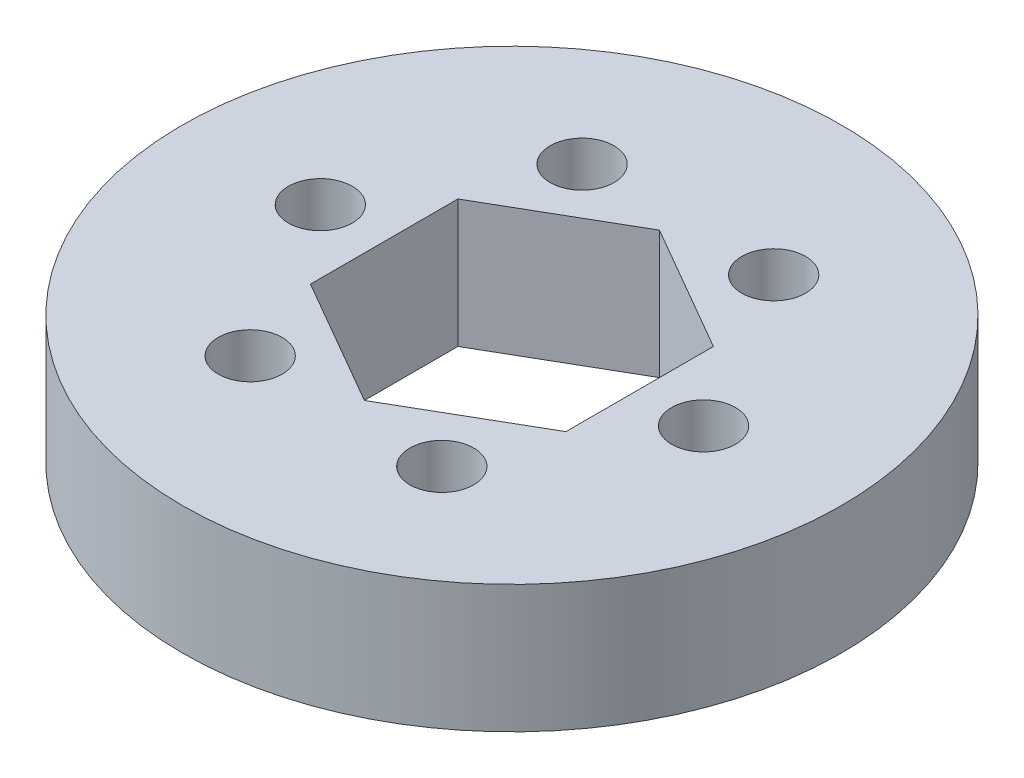
SolidWorks part; units mm, degrees
ref_plane "Front" through (0, 0, 0) normal (0, 0, 1) x (1, 0, 0)
ref_plane "Top" through (0, 0, 0) normal (0, 1, 0) x (1, 0, 0)
ref_plane "Right" through (0, 0, 0) normal (1, 0, 0) x (0, 0, -1)
sketch "Sketch1" plane through (0, 0, 0) normal (0, 1, 0) x (1, 0, 0)
  line L1 (0, 7.3323) -> (-6.35, 3.6662)
  line L2 (-6.35, 3.6662) -> (-6.35, -3.6662)
  line L3 (-6.35, -3.6662) -> (0, -7.3323)
  line L4 (0, -7.3323) -> (6.35, -3.6662)
  line L5 (6.35, -3.6662) -> (6.35, 3.6662)
  line L6 (6.35, 3.6662) -> (0, 7.3323)
  circle A0 centre (0, 0) radius 6.35 construction
  circle A1 centre (0, 0) radius 16.383
  dimension "D1" = 32.766
extrude "Boss-Extrude1" add sketch "Sketch1" along normal blind 6.35
sketch "Sketch2" plane through (0, 6.35, 0) normal (0, 1, 0) x (1, 0, 0)
  line L4 (0, 0) -> (6.35, 0) construction
  line L5 (6.35, -3.6662) -> (6.35, 3.6662) construction
  line L6 (0, 0) -> (0, 7.3323) construction
sketch "Sketch3" plane through (0, 6.35, 0) normal (0, 1, 0) x (1, 0, 0)
  line L0 (0, 0) -> (9.525, 0) construction
  circle A0 centre (9.525, 0) radius 1.5875
  circle A1 centre (4.7625, -8.2489) radius 1.5875
  circle A2 centre (-4.7625, -8.2489) radius 1.5875
  circle A3 centre (-9.525, 0) radius 1.5875
  circle A4 centre (-4.7625, 8.2489) radius 1.5875
  circle A5 centre (4.7625, 8.2489) radius 1.5875
  point P16 (0, 0)
  dimension "D1" = 3.175
  dimension "D2" = 9.525
  dimension "D3" = 6
extrude "Cut-Extrude1" cut sketch "Sketch3" against normal up to next
